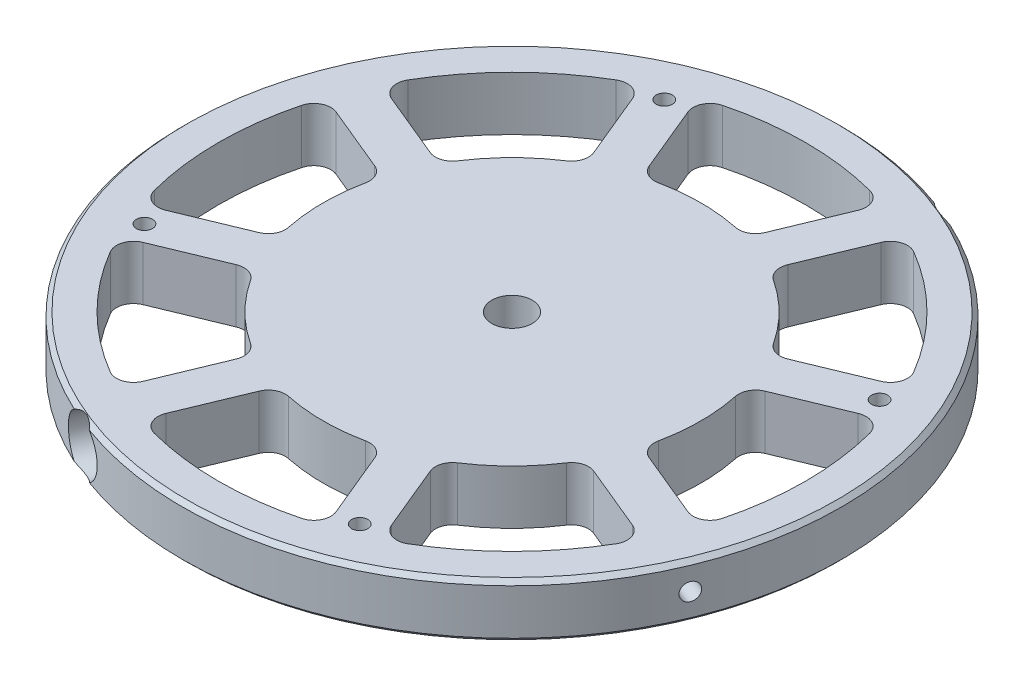
SolidWorks part; units mm, degrees
material "6061-T6 (SS)"
ref_plane "Front Plane" through (0, 0, 0) normal (0, 0, 1) x (1, 0, 0)
ref_plane "Top Plane" through (0, 0, 0) normal (0, 1, 0) x (1, 0, 0)
ref_plane "Right Plane" through (0, 0, 0) normal (1, 0, 0) x (0, 0, -1)
sketch "Sketch2" plane through (0, 0, 0) normal (1, 0, 0) x (0, 0, -1)
  line L0 (0, 0) -> (-77.55, 0)
  line L1 (-77.55, 0) -> (-77.55, 12.7)
  line L2 (-77.55, 12.7) -> (0, 12.7)
  line L5 (0, 12.7) -> (0, 0)
  dimension "D1" = 77.55
  dimension "D2" = 12.7
ref_axis "Axis1" through (0, -0.8888, 0) along (0, 1, 0)
revolve "Revolve1" add sketch "Sketch2" angle 360 about axis through (0, -0.8888, 0) along (0, 1, 0)
hole_wizard "#10-24 Tapped Hole2" positions "Sketch6" profile "Sketch7" tap size "#10-24" standard "ANSI Inch" end condition through all
sketch "Sketch6" plane through (0, 12.7, 0) normal (0, 1, 0) x (1, 0, 0)
  line L0 (0, 0) -> (-53.438, 129.0108) construction
  line L2 (0, 0) -> (0, 109.0908) construction
  point P0 (-25.3336, 61.1608)
  dimension "D1" = 22.5
  dimension "D2" = 66.2
sketch "Sketch7" plane through (-25.3336, 12.7, -61.1608) normal (1, 0, 0) x (0, 0, 1)
  line L0 (0, 0) -> (0, 12.7)
  line L1 (0, 12.7) -> (1.8986, 12.7)
  line L2 (1.8986, 12.7) -> (1.8986, 0)
  line L5 (1.8986, 0) -> (0, 0)
  line L11 (0, -6.35) -> (0, 107.95) construction
  dimension "Thread Major Dia." = 3.7973
  dimension "Thru Tap Drill Depth" = 12.7
pattern_circular "CirPattern3" count 4 over 360 about axis through (0, -0.8888, 0) along (0, 1, 0) of "#10-24 Tapped Hole2"
sketch "Sketch8" plane through (0, 12.7, 0) normal (0, 1, 0) x (1, 0, 0)
  line L4 (0, 0) -> (0, 93.9995) construction
  line L5 (0, 0) -> (113.8372, 0) construction
  line L6 (-12.2829, 42.7192) -> (-21.7355, 65.5398)
  line L7 (12.2829, 42.7192) -> (21.7355, 65.5398)
  line L8 (0, 0) -> (-25.3336, 61.1608) construction
  arc A0 (-12.2829, 42.7192) -> (12.2829, 42.7192) centre (0, 0) cw
  arc A1 (-21.7355, 65.5398) -> (21.7355, 65.5398) centre (0, 0) cw
  circle A2 centre (0, 0) radius 77.55 construction
  dimension "D1" = 44.45
  dimension "D2" = 8.5
  dimension "D3" = 5
extrude "Cut-Extrude1" cut sketch "Sketch8" against normal through all
fillet "Fillet1" radius 4 4 edges at (12.2829, 6.35, -42.7192) (21.7355, 6.35, -65.5398) (-12.2829, 6.35, -42.7192) (-21.7355, 6.35, -65.5398)
pattern_circular "CirPattern4" count 8 over 360 about axis through (0, -0.8888, 0) along (0, 1, 0) of "Cut-Extrude1", "Fillet1"
chamfer "Chamfer1" distance 1 angle 45 2 edges at (0, 0, -77.55) (0, 12.7, -77.55)
ref_plane "Plane1" through (0, 0, 0) normal (0.9239, 0, 0.3827) x (0, 1, 0)
hole_wizard "#20 (0.161) Diameter Hole1" positions "Sketch16" profile "Sketch15" hole size "#20" standard "ANSI Inch" end condition through all
sketch "Sketch16" plane through (0, 0, 0) normal (0.9239, 0, 0.3827) x (0, 1, 0)
  point P0 (6.35, 0)
  dimension "D1" = 6.35
sketch "Sketch15" plane through (0, 6.35, 0) normal (0, 1, 0) x (-0.3827, 0, 0.9239)
  line L0 (0, 0) -> (0, 101.324)
  line L1 (0, 101.324) -> (2.0447, 101.324)
  line L2 (2.0447, 101.324) -> (2.0447, 0)
  line L5 (2.0447, 0) -> (0, 0)
  line L11 (0, -6.35) -> (0, 107.95) construction
  dimension "Thru Hole Dia." = 4.0894
  dimension "Thru Hole Depth" = 101.324
ref_plane "Plane2" through (29.6771, 0, -71.6469) normal (0.3827, 0, -0.9239) x (-0.9239, 0, -0.3827)
sketch "Sketch19" plane through (29.6771, 0, -71.6469) normal (0.3827, 0, -0.9239) x (-0.9239, 0, -0.3827)
  line L0 (-76.55, 0) -> (76.55, 0) construction
  line L2 (0, -0.8888) -> (0, 13.5888) construction
  circle A0 centre (0, 6.35) radius 5.5625 construction
  circle A1 centre (0, 6.35) radius 6.25
  dimension "D1" = 12.5
  dimension "D2" = 6.35
extrude "Cut-Extrude3" cut sketch "Sketch19" against normal blind 5
pattern_circular "CirPattern5" count 2 over 360 about axis through (0, -0.8888, 0) along (0, 1, 0) of "Cut-Extrude3"
hole_wizard "#10-24 Tapped Hole1" positions "Sketch20" profile "Sketch21" tap size "#10-24" standard "ANSI Inch"
sketch "Sketch20" plane through (-27.7637, 0, 67.0275) normal (-0.3827, 0, 0.9239) x (0.9239, 0, 0.3827)
  circle A0 centre (0, 6.35) radius 6.25
  circle A1 centre (0, 6.35) radius 6.25 construction
  point P0 (0, 6.35)
sketch "Sketch21" plane through (-27.7637, 6.35, 67.0275) normal (0, 1, 0) x (0.9239, 0, 0.3827)
  line L0 (0, 0) -> (0, 51.9408)
  line L1 (0, 51.9408) -> (1.8986, 50.8)
  line L2 (1.8986, 50.8) -> (1.8986, 0)
  line L5 (1.8986, 0) -> (0, 0)
  line L10 (0, 51.9408) -> (-1.8986, 50.8) construction
  line L11 (0, -6.35) -> (0, 107.95) construction
  dimension "Tap Drill Dia." = 3.7973
  dimension "Tap Drill Depth" = 50.8
  dimension "Drill Angle" = 118
pattern_circular "CirPattern6" count 2 over 360 about axis through (0, -0.8888, 0) along (0, 1, 0) of "#10-24 Tapped Hole1"
sketch "Sketch22" plane through (0, 12.7, 0) normal (0, 1, 0) x (1, 0, 0)
  circle A0 centre (0, 0) radius 4.765
  dimension "D1" = 9.53
extrude "Cut-Extrude4" cut sketch "Sketch22" against normal blind 12.8
equation "\"TubeDiameter\" = 6.500in"
equation "\"D1@Sketch2\"=(\"TubeDiameter\"/2)-5mm"
equation "\"D2@Sketch6\"=66.2"
